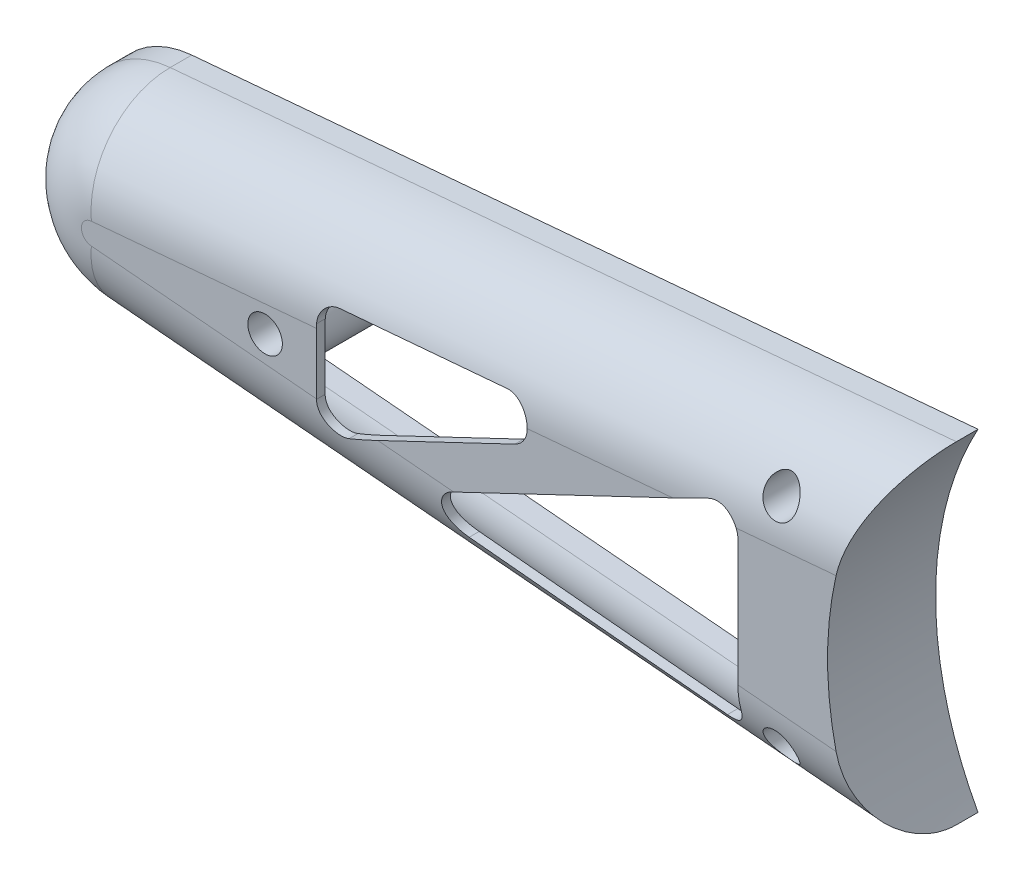
SolidWorks part; units mm, degrees
ref_plane "Front Plane" through (0, 0, 0) normal (0, 0, 1) x (1, 0, 0)
ref_plane "Top Plane" through (0, 0, 0) normal (0, 1, 0) x (1, 0, 0)
ref_plane "Right Plane" through (0, 0, 0) normal (1, 0, 0) x (0, 0, -1)
sketch "Sketch1" plane through (0, 0, 0) normal (0, 0, 1) x (1, 0, 0)
  line L0 (-100, 0) -> (100, 0) construction
  line L1 (-101.9688, 22.4137) -> (96.5, 39.8466)
  line L4 (96.5, -39.8466) -> (-101.9688, -22.4137)
  arc A0 (96.5, -39.8466) -> (96.5, 39.8466) centre (100, 0) ccw
  arc A1 (-101.9688, 22.4137) -> (-101.9688, -22.4137) centre (-100, 0) ccw
  dimension "D2" = 80
  dimension "D3" = 45
  dimension "D1" = 200
extrude "Boss-Extrude1" add sketch "Sketch1" along normal blind 25 and the other way blind 25
fillet "Fillet1" radius 20 8 edges at (-2.7344, -31.1301, -25) (140, 0, -25) (-2.7344, 31.1301, -25) (-122.5, 0, -25) (-2.7344, 31.1301, 25) (140, 0, 25) (-2.7344, -31.1301, 25) (-122.5, 0, 25)
shell "Shell1" thickness 2
sketch "Sketch2" plane through (0, 0, 25) normal (0, 0, 1) x (1, 0, 0)
  line L3 (49.4372, 13.583) -> (49.4372, -20.9242)
  line L4 (43.9049, -25.8958) -> (-15.1993, -19.5675)
  line L5 (-16.8188, -10.0826) -> (42.2854, 18.0963)
  line L6 (-2.1805, 6.8207) -> (-40.9454, -11.6611)
  line L7 (-48.0972, -7.1478) -> (-48.0972, 7.9923)
  line L8 (-43.5266, 12.9738) -> (-4.7617, 16.3156)
  arc A3 (49.4372, -20.9242) -> (43.9049, -25.8958) centre (44.4372, -20.9242) cw
  arc A4 (49.4372, 13.583) -> (42.2854, 18.0963) centre (44.4372, 13.583) ccw
  arc A5 (-15.1993, -19.5675) -> (-16.8188, -10.0826) centre (-14.667, -14.5959) cw
  arc A6 (-2.1805, 6.8207) -> (-4.7617, 16.3156) centre (-4.3323, 11.334) ccw
  arc A7 (-48.0972, 7.9923) -> (-43.5266, 12.9738) centre (-43.0972, 7.9923) cw
  arc A8 (-40.9454, -11.6611) -> (-48.0972, -7.1478) centre (-43.0972, -7.1478) cw
extrude "Cut-Extrude1" cut sketch "Sketch2" against normal through all
sketch "Sketch4" plane through (0, 0, 0) normal (0, 0, 1) x (1, 0, 0)
  line L0 (-60, 0) -> (57.5, 0) construction
  line L1 (57.5, 25) -> (57.5, -25) construction
  circle A0 centre (-60, 0) radius 7.5
  circle A1 centre (57.5, 25) radius 7.5
  circle A2 centre (57.5, -25) radius 7.5
  dimension "D1" = 15
  dimension "D2" = 50
  dimension "D3" = 60
  dimension "D4" = 57.5
extrude "Boss-Extrude2" add sketch "Sketch4" along normal up to next and the other way up to next
sketch "Sketch5" plane through (0, 0, 0) normal (0, 0, 1) x (1, 0, 0)
  circle A0 centre (57.5, 25) radius 1.75
  circle A1 centre (57.5, -25) radius 1.75
  circle A2 centre (-60, 0) radius 1.75
  dimension "D1" = 3.5
extrude "Cut-Extrude2" cut sketch "Sketch5" against normal through all both and the other way through all
sketch "Sketch6" plane through (0, 0, 25) normal (0, 0, 1) x (1, 0, 0)
  circle A0 centre (57.5, 25) radius 4
  circle A1 centre (57.5, -25) radius 4
  circle A2 centre (-60, 0) radius 4
  dimension "D1" = 8
extrude "Cut-Extrude3" cut sketch "Sketch6" against normal blind 12
mirror "Mirror1" about plane through (0, 0, 0) normal (0, 0, 1) of "Cut-Extrude3"
chamfer "Chamfer1" distance 2 angle 45 6 edges at (61.5, -25, 13) (61.5, 25, 13) (-56, 0, 13) (-56, 0, -13) (61.5, -25, -13) (61.5, 25, -13)
sketch "Sketch7" plane through (0, 0, 0) normal (0, 0, 1) x (1, 0, 0)
  line L1 (-171.6611, 90.4785) -> (189.7069, 90.4785)
  line L2 (-171.6611, 90.4785) -> (-171.6611, -100.8501)
  line L3 (-171.6611, -100.8501) -> (189.7069, -100.8501)
  line L4 (189.7069, 90.4785) -> (189.7069, -100.8501)
extrude "Cut-Extrude4" cut sketch "Sketch7" against normal through all
sketch "Sketch8" plane through (0, 0, 25) normal (0, 0, 1) x (1, 0, 0)
  line L0 (-101.9688, 22.4137) -> (96.5, 39.8466) construction
  line L1 (96.5, -39.8466) -> (-101.9688, -22.4137) construction
  line L2 (80, 38.3973) -> (80, -38.3973) construction
  line L3 (80, 38.3973) -> (96.5, 39.8466)
  line L4 (80, -38.3973) -> (96.5, -39.8466)
  arc A0 (80, 38.3973) -> (80, -38.3973) centre (150.183, 0) ccw
  arc A1 (96.5, -39.8466) -> (96.5, 39.8466) centre (100, 0) ccw construction
  arc A2 (96.5, -39.8466) -> (96.5, 39.8466) centre (100, 0) ccw
  dimension "D2" = 80
  dimension "D1" = 20
extrude "Cut-Extrude5" cut sketch "Sketch8" against normal through all
sketch "Sketch9" plane through (0, 0, 0) normal (0, 0, -1) x (-1, 0, 0)
  line L0 (-78.8885, -36.2919) -> (-76.215, -37.6529)
  line L2 (-78.8885, 36.2919) -> (-76.215, 37.6529)
  arc A0 (-78.8885, -36.2919) -> (-72.1499, -17.6307) centre (-150.183, 0) ccw construction
  arc A1 (-72.1499, -17.6307) -> (-72.1499, 17.6307) centre (-150.183, 0) ccw construction
  arc A2 (-72.1499, 17.6307) -> (-78.8885, 36.2919) centre (-150.183, 0) ccw construction
  arc A3 (-78.8885, -36.2919) -> (-72.1499, -17.6307) centre (-150.183, 0) ccw
  arc A4 (-72.1499, -17.6307) -> (-72.1499, 17.6307) centre (-150.183, 0) ccw
  arc A5 (-72.1499, 17.6307) -> (-78.8885, 36.2919) centre (-150.183, 0) ccw
  arc A6 (-76.215, -37.6529) -> (-69.2237, -18.2919) centre (-150.183, 0) ccw
  arc A7 (-69.2237, -18.2919) -> (-69.2237, 18.2919) centre (-150.183, 0) ccw
  arc A8 (-69.2237, 18.2919) -> (-76.215, 37.6529) centre (-150.183, 0) ccw
  point P14 (-76.215, -37.6529)
  dimension "D1" = 3
extrude "Boss-Extrude3" add sketch "Sketch9" against normal up to next
